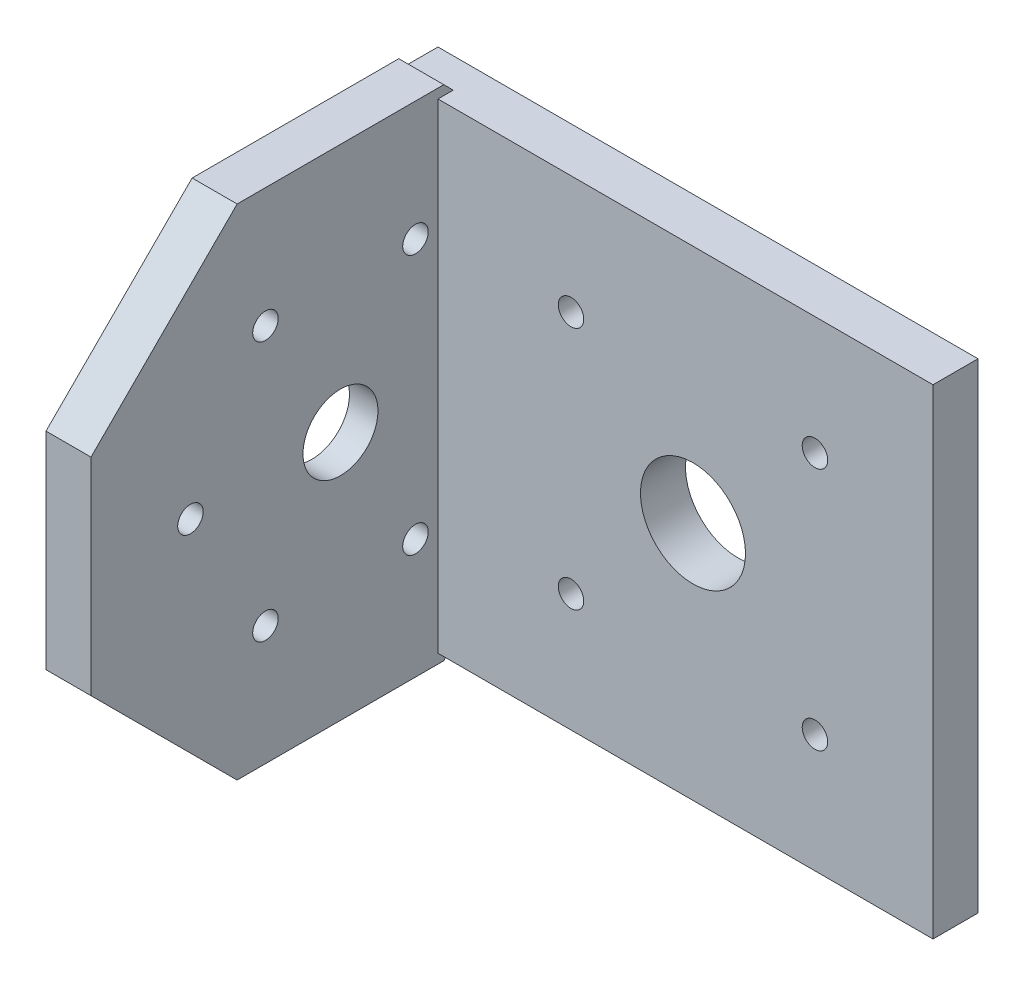
SolidWorks part; units mm, degrees
material "6061-T6 (SS)"
ref_plane "Front Plane" through (0, 0, 0) normal (0, 0, 1) x (1, 0, 0)
ref_plane "Top Plane" through (0, 0, 0) normal (0, 1, 0) x (1, 0, 0)
ref_plane "Right Plane" through (0, 0, 0) normal (1, 0, 0) x (0, 0, -1)
ref_plane "PL_Roll_Plate_base" through (-40, 0, 0) normal (1, 0, 0) x (0, 0, -1)
sketch "SK_Roll_Plate" plane through (-40, 0, 0) normal (1, 0, 0) x (0, 0, -1)
  line L0 (-13.7766, -33.2597) -> (-33.2597, -13.7766)
  line L1 (-33.2597, -13.7766) -> (-33.2597, 13.7766)
  line L2 (-33.2597, 13.7766) -> (-13.7766, 33.2597)
  line L3 (-13.7766, 33.2597) -> (13.7766, 33.2597)
  line L4 (13.7766, 33.2597) -> (33.2597, 13.7766)
  line L5 (33.2597, 13.7766) -> (33.2597, -13.7766)
  line L6 (33.2597, -13.7766) -> (13.7766, -33.2597)
  line L7 (13.7766, -33.2597) -> (-13.7766, -33.2597)
  circle A0 centre (20, 0) radius 1.7
  circle A1 centre (10, -17.3205) radius 1.7
  circle A2 centre (-10, -17.3205) radius 1.7
  circle A3 centre (-20, 0) radius 1.7
  circle A4 centre (-10, 17.3205) radius 1.7
  circle A5 centre (10, 17.3205) radius 1.7
  circle A6 centre (0, 0) radius 5
  dimension "D17_SK_Roll_Plate" = 3.4
  dimension "D19_SK_Roll_Plate" = 3.4
  dimension "D22_SK_Roll_Plate" = 3.4
  dimension "D25_SK_Roll_Plate" = 3.4
  dimension "D27_SK_Roll_Plate" = 3.4
  dimension "D30_SK_Roll_Plate" = 3.4
  dimension "D33_SK_Roll_Plate" = 10
  dimension "P1" = 13.7766
  dimension "P2" = 33.2597
  dimension "P3" = 33.2597
  dimension "P4" = 13.7766
  dimension "P5" = 33.2597
  dimension "P6" = 13.7766
  dimension "P7" = 13.7766
  dimension "P8" = 33.2597
  dimension "P9" = 13.7766
  dimension "P10" = 33.2597
  dimension "P11" = 33.2597
  dimension "P12" = 13.7766
  dimension "P13" = 33.2597
  dimension "P14" = 13.7766
  dimension "P15" = 13.7766
  dimension "P16" = 33.2597
  dimension "P18" = 20
  dimension "P20" = 10
  dimension "P21" = 17.3205
  dimension "P23" = 10
  dimension "P24" = 17.3205
  dimension "P26" = 20
  dimension "P28" = 10
  dimension "P29" = 17.3205
  dimension "P31" = 10
  dimension "P32" = 17.3205
extrude "Roll_Plate" add sketch "SK_Roll_Plate" along normal blind 6
ref_plane "PL_Yaw_Plate_base" through (0, 0, -19) normal (0, 0, 1) x (1, 0, 0)
sketch "SK_Yaw_Plate" plane through (0, 0, -19) normal (0, 0, 1) x (1, 0, 0)
  line L0 (-40, 32) -> (32, 32)
  line L1 (32, 32) -> (32, -32)
  line L2 (32, -32) -> (-40, -32)
  line L3 (-40, -32) -> (-40, 32)
  circle A0 centre (16.2635, -16.2635) radius 1.7
  circle A1 centre (-16.2635, -16.2635) radius 1.7
  circle A2 centre (-16.2635, 16.2635) radius 1.7
  circle A3 centre (16.2635, 16.2635) radius 1.7
  circle A4 centre (0, 0) radius 7
  dimension "D9_SK_Yaw_Plate" = 3.4
  dimension "D12_SK_Yaw_Plate" = 3.4
  dimension "D15_SK_Yaw_Plate" = 3.4
  dimension "D18_SK_Yaw_Plate" = 3.4
  dimension "D21_SK_Yaw_Plate" = 14
  dimension "P1" = 40
  dimension "P2" = 32
  dimension "P3" = 32
  dimension "P4" = 32
  dimension "P5" = 32
  dimension "P6" = 32
  dimension "P7" = 40
  dimension "P8" = 32
  dimension "P10" = 16.2635
  dimension "P11" = 16.2635
  dimension "P13" = 16.2635
  dimension "P14" = 16.2635
  dimension "P16" = 16.2635
  dimension "P17" = 16.2635
  dimension "P19" = 16.2635
  dimension "P20" = 16.2635
extrude "Yaw_Plate" add sketch "SK_Yaw_Plate" along normal blind 6
ref_plane "PL_Roll_Pilot_Recess_base" through (-40, 0, 0) normal (1, 0, 0) x (0, 0, -1)
sketch "SK_Roll_Pilot_Recess" plane through (-40, 0, 0) normal (1, 0, 0) x (0, 0, -1)
  circle A0 centre (0, 0) radius 15.15
  dimension "D1_SK_Roll_Pilot_Recess" = 30.3
extrude "Roll_Pilot_Recess" cut sketch "SK_Roll_Pilot_Recess" along normal blind 2.2
equation "\"Roll_face_x\"= -40"
equation "\"Yaw_rear_z\"= -19"
